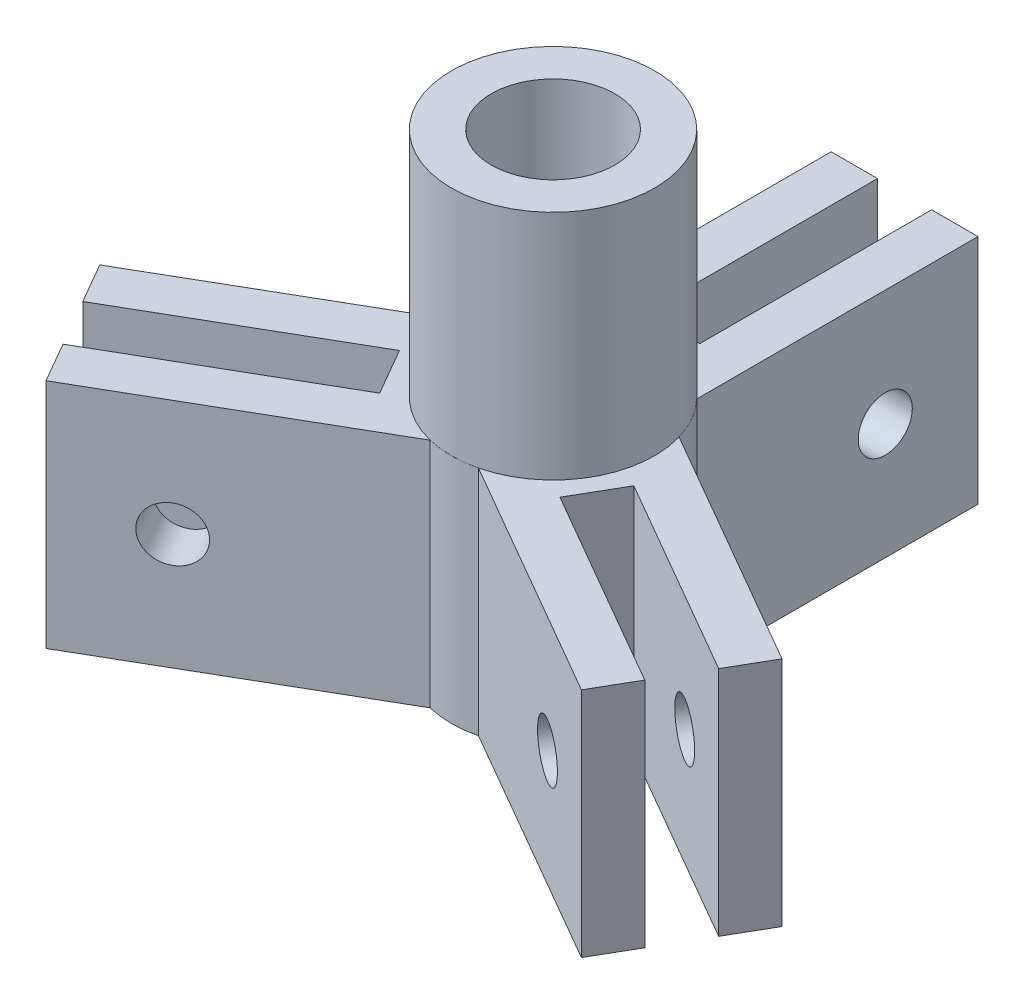
SolidWorks part; units mm, degrees
ref_plane "前基準面" through (0, 0, 0) normal (0, 0, 1) x (1, 0, 0)
ref_plane "上基準面" through (0, 0, 0) normal (0, 1, 0) x (1, 0, 0)
ref_plane "右基準面" through (0, 0, 0) normal (1, 0, 0) x (0, 0, -1)
sketch "草圖1" plane through (0, 0, 0) normal (0, 1, 0) x (1, 0, 0)
  line L0 (6.315, 1.8389) -> (22.0705, -7.2576)
  line L2 (-4.75, 4.5495) -> (-4.75, 22.7424)
  line L3 (-4.75, 22.7424) -> (-1.75, 22.7424)
  line L4 (4.75, 4.5495) -> (4.75, 22.7424)
  line L5 (22.0705, -7.2576) -> (20.5705, -9.8557)
  line L7 (-1.75, 22.7424) -> (-1.75, 7.7424)
  line L8 (-1.75, 7.7424) -> (1.75, 7.7424)
  line L9 (1.75, 22.7424) -> (1.75, 7.7424)
  line L10 (1.75, 22.7424) -> (4.75, 22.7424)
  line L11 (20.5705, -9.8557) -> (7.5801, -2.3557)
  line L12 (7.5801, -2.3557) -> (5.8301, -5.3868)
  line L13 (18.8205, -12.8868) -> (5.8301, -5.3868)
  line L14 (18.8205, -12.8868) -> (17.3205, -15.4848)
  line L15 (1.565, -6.3884) -> (17.3205, -15.4848)
  line L17 (-1.565, -6.3884) -> (-17.3205, -15.4848)
  line L18 (-17.3205, -15.4848) -> (-18.8205, -12.8868)
  line L19 (-18.8205, -12.8868) -> (-5.8301, -5.3868)
  line L20 (-5.8301, -5.3868) -> (-7.5801, -2.3557)
  line L21 (-20.5705, -9.8557) -> (-7.5801, -2.3557)
  line L22 (-20.5705, -9.8557) -> (-22.0705, -7.2576)
  line L23 (-6.315, 1.8389) -> (-22.0705, -7.2576)
  circle A0 centre (0, 0) radius 4
  arc A1 (-1.565, -6.3884) -> (1.565, -6.3884) centre (0, 0) ccw
  arc A2 (6.315, 1.8389) -> (4.75, 4.5495) centre (0, 0) ccw
  arc A3 (-4.75, 4.5495) -> (-6.315, 1.8389) centre (0, 0) ccw
  point P4 (0, 0)
  point P29 (0, 0)
  dimension "D8" = 8
  dimension "D9" = 13.1545
  dimension "D1" = 18.1929
  dimension "D2" = 9.5
  dimension "D3" = 3.5
  dimension "D4" = 15
  dimension "D5" = 3
  dimension "D7" = 18.1929
  dimension "D6" = 3
extrude "填料-伸長2" add sketch "草圖1" along normal blind 15
sketch "草圖2" plane through (0, 15, 0) normal (0, 1, 0) x (1, 0, 0)
  circle A0 centre (0, 0) radius 6.575
  circle A1 centre (0, 0) radius 4
  dimension "D1" = 13.15
  dimension "D2" = 8
extrude "填料-伸長3" add sketch "草圖2" along normal blind 15
sketch "草圖3" plane through (4.75, 0, 0) normal (1, 0, 0) x (0, 0, -1)
  line L0 (22.7424, 15) -> (22.7424, 0) construction
  circle A0 centre (16.7424, 7.5) radius 1.75
  point P4 (0, 0)
  point P5 (22.7424, 7.5)
  dimension "D1" = 3.5
  dimension "D2" = 6
extrude "除料-伸長1" cut sketch "草圖3" against normal blind 15
sketch "草圖4" plane through (-2.375, 0, -4.1136) normal (-0.5, 0, -0.866) x (-0.866, 0, 0.5)
  line L0 (22.7424, 15) -> (22.7424, 0) construction
  circle A0 centre (16.7424, 7.5) radius 1.75
  point P4 (0, 0)
  point P5 (22.7424, 7.5)
  dimension "D1" = 3.5
  dimension "D2" = 6
extrude "除料-伸長2" cut sketch "草圖4" against normal blind 15
sketch "草圖5" plane through (-2.375, 0, 4.1136) normal (-0.5, 0, 0.866) x (0.866, 0, 0.5)
  line L0 (22.7424, 15) -> (22.7424, 0) construction
  circle A0 centre (16.7424, 7.5) radius 1.75
  point P4 (22.7424, 7.5)
  dimension "D1" = 3.5
  dimension "D2" = 6
extrude "除料-伸長3" cut sketch "草圖5" against normal blind 15
